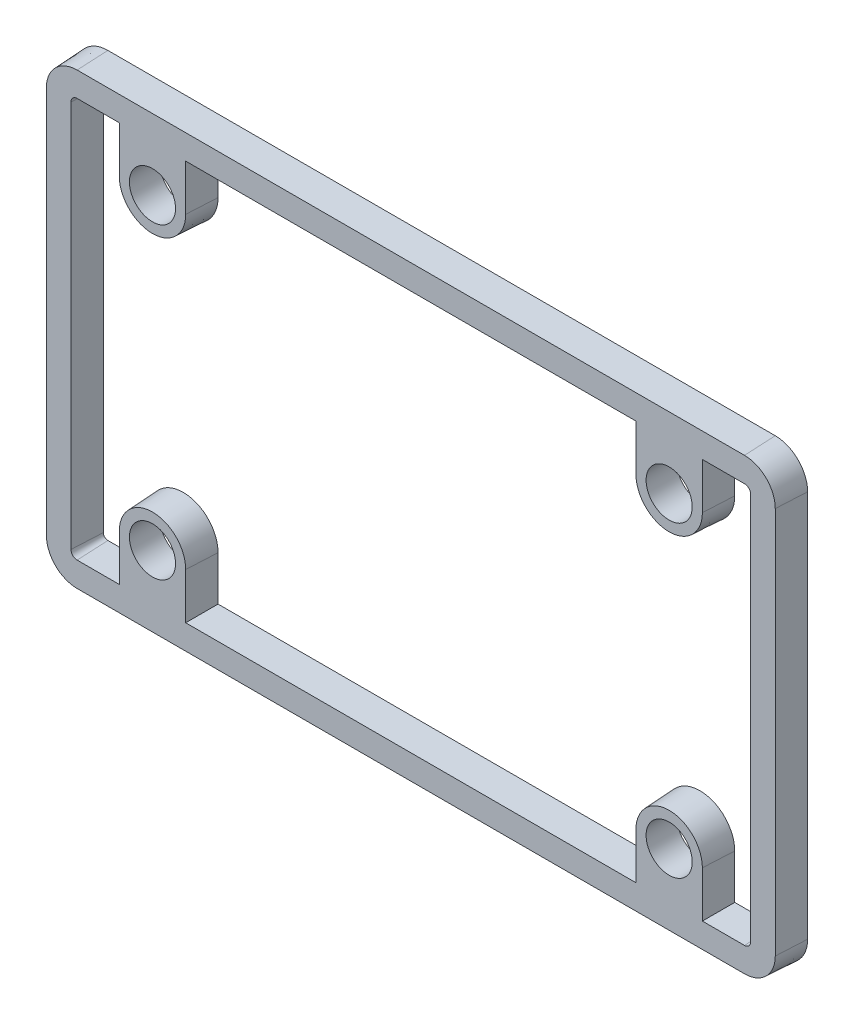
SolidWorks part; units mm, degrees
material "ｼﾘｺﾝ ｺﾞﾑ"
ref_plane "正面" through (0, 0, 0) normal (0, 0, 1) x (1, 0, 0)
ref_plane "平面" through (0, 0, 0) normal (0, 1, 0) x (1, 0, 0)
ref_plane "右側面" through (0, 0, 0) normal (1, 0, 0) x (0, 0, -1)
sketch "ｽｹｯﾁ1" plane through (0, 0, 0) normal (0, 0, 1) x (1, 0, 0)
  line L0 (0, 0) -> (0, -46915.4499) construction
  line L1 (0, 0) -> (46915.4499, 0) construction
  line L2 (-59.25, -31.5) -> (-59.25, 31.5)
  line L3 (-54.25, 36.5) -> (54.25, 36.5)
  line L4 (-54.25, 32.5) -> (-47.4, 32.5)
  line L5 (-54.25, -36.5) -> (54.25, -36.5)
  line L6 (55.25, -31.5) -> (55.25, 31.5)
  line L7 (59.25, -31.5) -> (59.25, 31.5)
  line L8 (-54.25, -32.5) -> (-47.4, -32.5)
  line L9 (-55.25, -31.5) -> (-55.25, 31.5)
  line L10 (-47.4, 25) -> (-47.4, 32.5)
  line L11 (-36.6, 25) -> (-36.6, 32.5)
  line L12 (36.6, 25) -> (36.6, 32.5)
  line L13 (47.4, 25) -> (47.4, 32.5)
  line L14 (47.4, -25) -> (47.4, -32.5)
  line L15 (36.6, -25) -> (36.6, -32.5)
  line L16 (-47.4, -25) -> (-47.4, -32.5)
  line L17 (-36.6, -25) -> (-36.6, -32.5)
  line L18 (-36.6, -32.5) -> (36.6, -32.5)
  line L19 (-54.25, -32.5) -> (54.25, -32.5) construction
  line L20 (47.4, -32.5) -> (54.25, -32.5)
  line L21 (47.4, 32.5) -> (54.25, 32.5)
  line L22 (-54.25, 32.5) -> (54.25, 32.5) construction
  line L23 (-36.6, 32.5) -> (36.6, 32.5)
  arc A0 (54.25, 32.5) -> (55.25, 31.5) centre (54.25, 31.5) cw
  arc A1 (54.25, -32.5) -> (55.25, -31.5) centre (54.25, -31.5) ccw
  arc A2 (54.25, -36.5) -> (59.25, -31.5) centre (54.25, -31.5) ccw
  arc A3 (54.25, 36.5) -> (59.25, 31.5) centre (54.25, 31.5) cw
  arc A4 (-59.25, 31.5) -> (-54.25, 36.5) centre (-54.25, 31.5) cw
  arc A5 (-55.25, -31.5) -> (-54.25, -32.5) centre (-54.25, -31.5) ccw
  arc A6 (-55.25, 31.5) -> (-54.25, 32.5) centre (-54.25, 31.5) cw
  circle A7 centre (-42, 25) radius 3.75
  circle A8 centre (-42, -25) radius 3.75
  arc A9 (-59.25, -31.5) -> (-54.25, -36.5) centre (-54.25, -31.5) ccw
  circle A10 centre (42, -25) radius 3.75
  circle A11 centre (42, 25) radius 3.75
  arc A16 (-47.4, 25) -> (-36.6, 25) centre (-42, 25) ccw
  arc A17 (-36.6, -25) -> (-47.4, -25) centre (-42, -25) ccw
  arc A18 (47.4, -25) -> (36.6, -25) centre (42, -25) ccw
  arc A19 (36.6, 25) -> (47.4, 25) centre (42, 25) ccw
  point P25 (59.25, 36.5)
  point P28 (-59.25, 36.5)
  point P41 (-59.25, -36.5)
  point P62 (-42, 25)
  point P63 (42, -25)
  point P64 (42, 25)
  point P65 (-42, -25)
  dimension "D3" = 4
  dimension "D4" = 7.5
  dimension "D8" = 5
  dimension "D17" = 10.8
  dimension "D1" = 118.5
  dimension "D2" = 73
  dimension "D15" = 50
  dimension "D16" = 84
extrude "ﾎﾞｽ - 押し出し5" add sketch "ｽｹｯﾁ1" against normal blind 5 draft 3 contours A4 L3 A3 L7 A2 L5 A9 L2 | L23 L12 A19 L13 L21 A0 L6 A1 L20 L14 A18 L15 L18 L17 A17 L16 L8 A5 L9 A6 L4 L10 A16 L11 draft outward yes
extrude "ｶｯﾄ - 押し出し1" cut sketch "ｽｹｯﾁ1<9>" against normal through all contours A7 | A11 | A10 | A8 region at (-42, 25, 0) region at (-42, -25, 0) region at (42, -25, 0) region at (42, 25, 0)
sketch "ｽｹｯﾁ1<9>" plane through (0, 0, 0) normal (0, 0, 1) x (1, 0, 0) same geometry as "ｽｹｯﾁ1"
